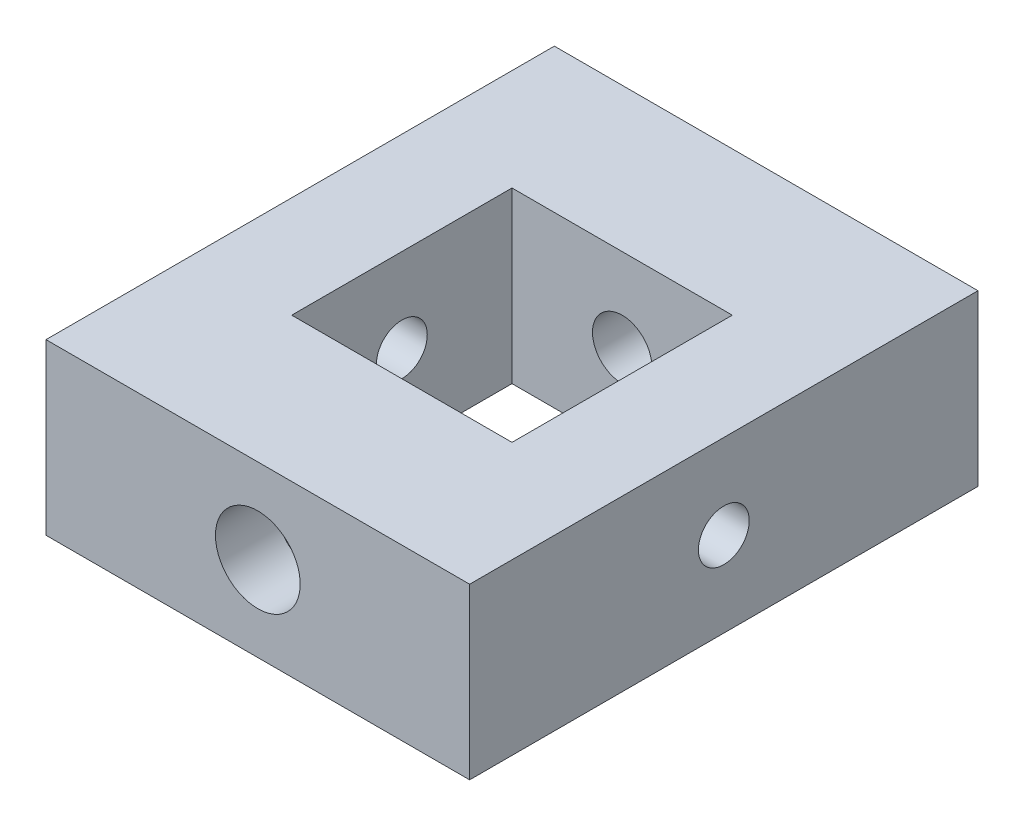
SolidWorks part; units mm, degrees
ref_plane "前视基准面" through (0, 0, 0) normal (0, 0, 1) x (1, 0, 0)
ref_plane "上视基准面" through (0, 0, 0) normal (0, 1, 0) x (1, 0, 0)
ref_plane "右视基准面" through (0, 0, 0) normal (1, 0, 0) x (0, 0, -1)
other "Configuration Table"
sketch "草图1" plane through (0, 0, 0) normal (0, 1, 0) x (1, 0, 0)
  line L5 (-2.6, -2.6) -> (2.6, -2.6)
  line L6 (-2.6, -2.6) -> (-2.6, 2.6)
  line L7 (-2.6, 2.6) -> (2.6, 2.6)
  line L8 (2.6, -2.6) -> (2.6, 2.6)
  line L9 (-2.6, -2.6) -> (2.6, 2.6) construction
  line L10 (-2.6, 2.6) -> (2.6, -2.6) construction
  line L11 (-5, -6) -> (5, -6)
  line L12 (-5, -6) -> (-5, 6)
  line L13 (-5, 6) -> (5, 6)
  line L14 (5, -6) -> (5, 6)
  line L15 (-5, -6) -> (5, 6) construction
  line L16 (-5, 6) -> (5, -6) construction
  point P0 (0, 0)
  point P1 (0, 0)
  dimension "D1" = 5.2
  dimension "D2" = 12
  dimension "D3" = 10
extrude "凸台-拉伸1" add sketch "草图1" along normal blind 4 contours L11 L14 L13 L12 | L5 L8 L7 L6
sketch "草图2" plane through (5, 0, 0) normal (1, 0, 0) x (0, 0, -1)
  circle A0 centre (0, 2) radius 0.6
  point P2 (0, 2)
  point P4 (0, 0)
  point P7 (0, 0)
  dimension "D1" = 1.2
extrude "切除-拉伸1" cut sketch "草图2" against normal through all
sketch "草图3" plane through (0, 0, -6) normal (0, 0, -1) x (-1, 0, 0)
  circle A0 centre (0, 2) radius 1
  circle A1 centre (0, 2) radius 0.7
  point P3 (0, 2)
  dimension "D1" = 1.4
  dimension "D2" = 2
extrude "切除-拉伸2" cut sketch "草图3" against normal through all contours A1
extrude "切除-拉伸3" cut sketch "草图3<3>" against normal offset from surface (1.4 mm away) 2 contours A0 up to face at (-0.7, 2, -2.6)
sketch "草图3<3>" plane through (0, 0, -6) normal (0, 0, -1) x (-1, 0, 0) same geometry as "草图3"
extrude "切除-拉伸4" cut sketch "草图3<4>" along normal offset from surface (1.4 mm away) 2 from surface contours A0 up to face at (-0.7, 2, 2.6) starting at face at (-0.7, 2, 6)
sketch "草图3<4>" plane through (0, 0, -6) normal (0, 0, -1) x (-1, 0, 0) same geometry as "草图3"
